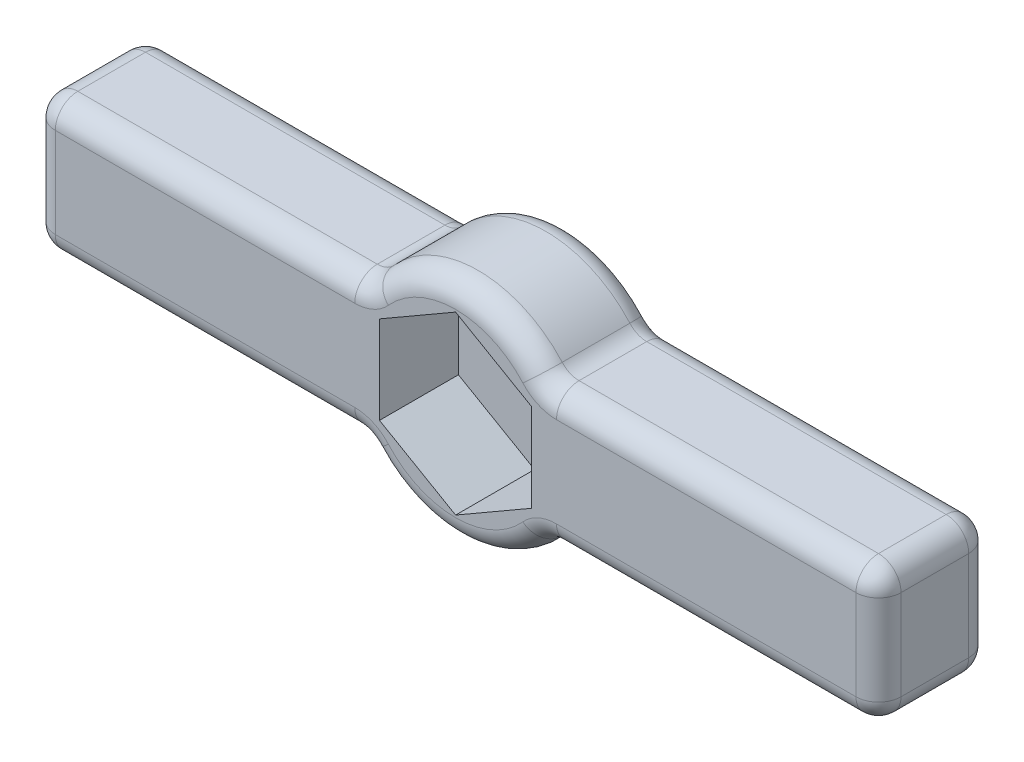
SolidWorks part; units mm, degrees
ref_plane "Front Plane" through (0, 0, 0) normal (0, 0, 1) x (1, 0, 0)
ref_plane "Top Plane" through (0, 0, 0) normal (0, 1, 0) x (1, 0, 0)
ref_plane "Right Plane" through (0, 0, 0) normal (1, 0, 0) x (0, 0, -1)
sketch "Sketch1" plane through (0, 0, 0) normal (0, 0, 1) x (1, 0, 0)
  line L1 (-37.5, -6) -> (37.5, -6)
  line L2 (-37.5, -6) -> (-37.5, 6)
  line L3 (-37.5, 6) -> (37.5, 6)
  line L4 (37.5, -6) -> (37.5, 6)
  line L5 (-37.5, -6) -> (37.5, 6) construction
  line L6 (-37.5, 6) -> (37.5, -6) construction
  point P0 (0, 0)
  dimension "D1" = 12
  dimension "D2" = 75
extrude "Boss-Extrude1" add sketch "Sketch1" along normal blind 10
sketch "Sketch2" plane through (0, 0, 10) normal (0, 0, 1) x (1, 0, 0)
  line L1 (0, -7.7942) -> (6.75, -3.8971)
  line L2 (6.75, -3.8971) -> (6.75, 3.8971)
  line L3 (6.75, 3.8971) -> (0, 7.7942)
  line L4 (0, 7.7942) -> (-6.75, 3.8971)
  line L5 (-6.75, 3.8971) -> (-6.75, -3.8971)
  line L6 (-6.75, -3.8971) -> (0, -7.7942)
  circle A0 centre (0, 0) radius 6.75 construction
  circle A1 centre (0, 0) radius 10.2013 construction
  dimension "D1" = 13.5
extrude "Cut-Extrude1" cut sketch "Sketch2" against normal blind 7
sketch "Sketch3" plane through (0, 0, 0) normal (0, 0, -1) x (-1, 0, 0)
  line L1 (0, -7.7942) -> (6.75, -3.8971)
  line L2 (6.75, -3.8971) -> (6.75, 3.8971)
  line L3 (6.75, 3.8971) -> (0, 7.7942)
  line L4 (0, 7.7942) -> (-6.75, 3.8971)
  line L5 (-6.75, 3.8971) -> (-6.75, -3.8971)
  line L6 (-6.75, -3.8971) -> (0, -7.7942)
  circle A0 centre (0, 0) radius 10
  circle A1 centre (0, 0) radius 6.75 construction
  dimension "D1" = 13.5
  dimension "D2" = 20
extrude "Boss-Extrude2" add sketch "Sketch3" against normal blind 10
sketch "Sketch4" plane through (0, 0, 0) normal (0, 0, -1) x (-1, 0, 0)
  line L0 (3.1077, 6) -> (0, 7.7942) construction
  line L1 (3.1077, 6) -> (0, 7.7942)
  line L2 (-3.1077, 6) -> (3.1077, 6) construction
  line L3 (-3.1077, 6) -> (3.1077, 6)
  line L4 (0, 7.7942) -> (-3.1077, 6) construction
  line L5 (0, 7.7942) -> (-3.1077, 6)
  line L6 (0, -7.7942) -> (3.1077, -6) construction
  line L7 (-3.1077, -6) -> (0, -7.7942) construction
  line L8 (3.1077, -6) -> (-3.1077, -6) construction
  line L9 (0, -7.7942) -> (3.1077, -6)
  line L10 (-3.1077, -6) -> (0, -7.7942)
  line L11 (3.1077, -6) -> (-3.1077, -6)
extrude "Boss-Extrude3" add sketch "Sketch4" against normal up to surface (3 mm away) up to face at (0, 0, 3)
fillet "Fillet1" radius 2 24 edges at (22.75, 6, 10) (37.5, 0, 10) (22.75, -6, 10) (0, -10, 10) (-22.75, -6, 10) (-37.5, 0, 10) (-22.75, 6, 10) (0, 10, 10) (8, 6, 5) (-8, 6, 5) (-8, -6, 5) (8, -6, 5) (-37.5, -6, 5) (-37.5, 6, 5) (-37.5, 0, 0) (0, -10, 0) (-22.75, -6, 0) (0, 10, 0) (-22.75, 6, 0) (22.75, 6, 0) (22.75, -6, 0) (37.5, 0, 0) (37.5, 6, 5) (37.5, -6, 5)
